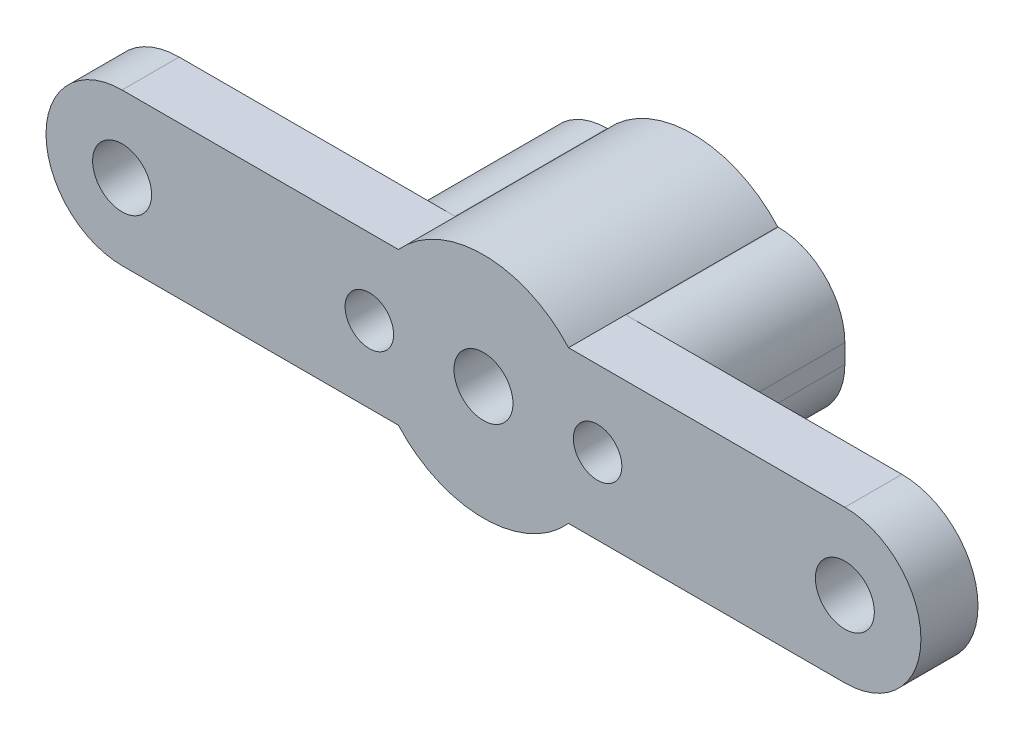
SolidWorks part; units mm, degrees
ref_plane "前视基准面" through (0, 0, 0) normal (0, 0, 1) x (1, 0, 0)
ref_plane "上视基准面" through (0, 0, 0) normal (0, 1, 0) x (1, 0, 0)
ref_plane "右视基准面" through (0, 0, 0) normal (1, 0, 0) x (0, 0, -1)
sketch "草图1" plane through (0, 0, 0) normal (0, 0, 1) x (1, 0, 0)
  line L0 (4.4721, 4) -> (19, 4)
  line L1 (-19, -4) -> (-4.4721, -4)
  line L2 (4.4721, -4) -> (19, -4)
  line L3 (-19, 4) -> (-4.4721, 4)
  circle A0 centre (0, 0) radius 1.55
  circle A1 centre (19, 0) radius 1.55
  circle A2 centre (-19, 0) radius 1.55
  arc A3 (-19, 4) -> (-19, -4) centre (-19, 0) ccw
  arc A4 (19, -4) -> (19, 4) centre (19, 0) ccw
  arc A5 (-4.4721, -4) -> (4.4721, -4) centre (0, 0) ccw
  arc A6 (4.4721, 4) -> (-4.4721, 4) centre (0, 0) ccw
  circle A7 centre (-6, 0) radius 1.275
  circle A8 centre (6, 0) radius 1.275
  dimension "D3" = 3.1
  dimension "D4" = 3.1
  dimension "D5" = 3.1
  dimension "D8" = 12
  dimension "D7" = 8
  dimension "D9" = 4
  dimension "D6" = 8
  dimension "D11" = 2.55
  dimension "D12" = 2.55
  dimension "D1" = 19
  dimension "D2" = 19
  dimension "D10" = 4
  dimension "D13" = 6
  dimension "D14" = 6
extrude "凸台-拉伸1" add sketch "草图1" along normal blind 3
sketch "草图2" plane through (0, 0, 0) normal (0, 0, -1) x (-1, 0, 0)
  line L0 (-19, 4) -> (-4.4721, 4) construction
  line L1 (-8, 4) -> (-4.4721, 4)
  line L2 (-8, 4) -> (-8, -4)
  line L3 (-8, -4) -> (-4.4721, -4)
  line L4 (8, 4) -> (8, -4)
  line L5 (19, -4) -> (4.4721, -4) construction
  line L6 (4.4721, 4) -> (8, 4)
  line L7 (4.4721, -4) -> (8, -4)
  arc A0 (-4.4721, -4) -> (4.4721, -4) centre (0, 0) ccw
  circle A1 centre (0, 0) radius 1.55
  circle A2 centre (-6, 0) radius 1.275
  circle A3 centre (6, 0) radius 1.275
  arc A4 (4.4721, 4) -> (-4.4721, 4) centre (0, 0) ccw
  dimension "D1" = 3.1
  dimension "D2" = 12
  dimension "D3" = 2.55
  dimension "D6" = 2.55
  dimension "D4" = 8
  dimension "D5" = 8
extrude "凸台-拉伸2" add sketch "草图2" along normal blind 8
fillet "圆角1" radius 3.5 4 edges
